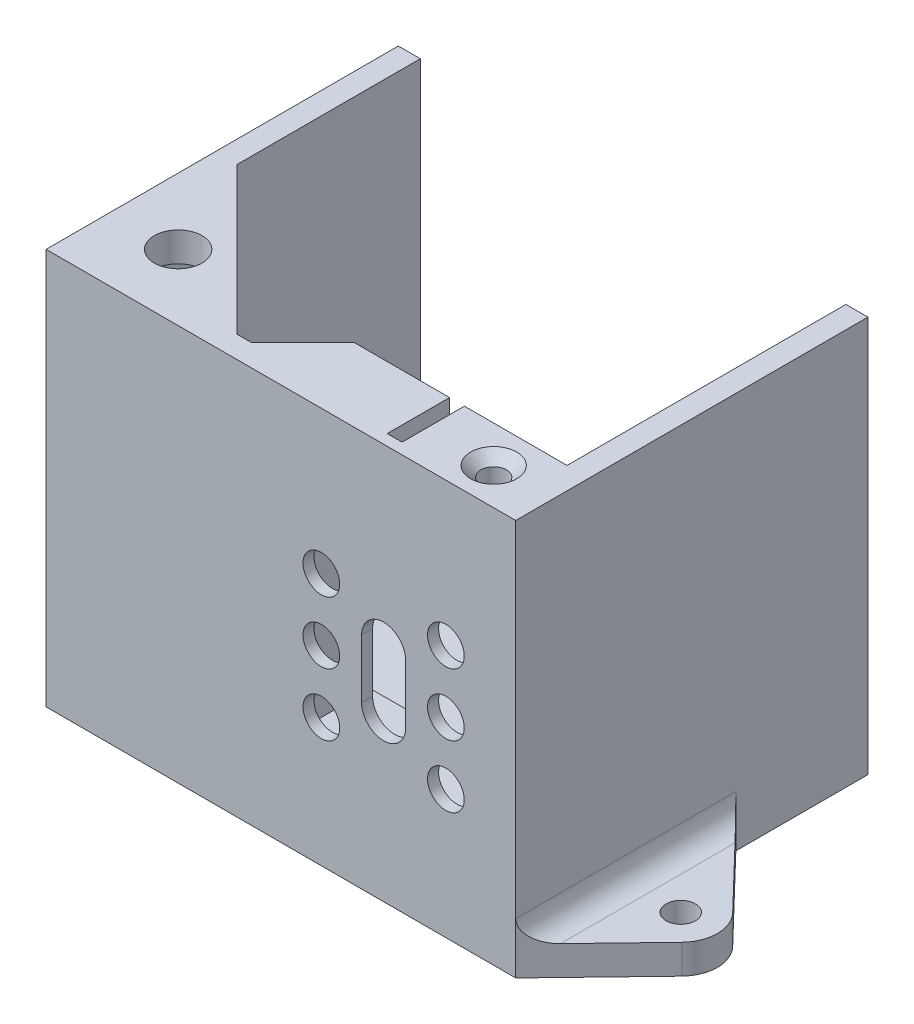
SolidWorks part; units mm, degrees
ref_plane "Płaszczyzna przednia" through (0, 0, 0) normal (0, 0, 1) x (1, 0, 0)
ref_plane "Płaszczyzna górna" through (0, 0, 0) normal (0, 1, 0) x (1, 0, 0)
ref_plane "Płaszczyzna prawa" through (0, 0, 0) normal (1, 0, 0) x (0, 0, -1)
sketch "Sketch1" plane through (0, 0, 0) normal (0, 1, 0) x (1, 0, 0)
  line L1 (-32, 24) -> (32, 24)
  line L2 (-32, 24) -> (-32, -24)
  line L3 (-32, -24) -> (32, -24)
  line L4 (32, 24) -> (32, -24)
  line L5 (-32, 24) -> (32, -24) construction
  line L6 (-32, -24) -> (32, 24) construction
  point P0 (0, 0)
  dimension "D1" = 64
  dimension "D2" = 48
extrude "Boss-Extrude1" add sketch "Sketch1" along normal blind 4
sketch "Sketch2" plane through (0, 0, 0) normal (0, -1, 0) x (1, 0, 0)
  line L9 (-20.6514, -16) -> (-22.3257, -13.1)
  line L10 (-22.3257, -13.1) -> (-25.6743, -13.1)
  line L11 (-25.6743, -13.1) -> (-27.3486, -16)
  line L12 (-27.3486, -16) -> (-25.6743, -18.9)
  line L13 (-25.6743, -18.9) -> (-22.3257, -18.9)
  line L14 (-22.3257, -18.9) -> (-20.6514, -16)
  line L15 (-32, -24) -> (-32, 24) construction
  line L16 (32, -24) -> (-32, -24) construction
  circle A0 centre (-24, -16) radius 2.9 construction
  dimension "D3" = 5.8
  dimension "D1" = 8
  dimension "D2" = 8
extrude "Cut-Extrude1" cut sketch "Sketch2" against normal blind 2.4
sketch "Sketch4" plane through (0, 0, 0) normal (0, -1, 0) x (1, 0, 0)
  line L0 (-32, -24) -> (-32, 24) construction
  line L1 (9.3486, 10) -> (7.6743, 12.9)
  line L2 (7.6743, 12.9) -> (4.3257, 12.9)
  line L3 (4.3257, 12.9) -> (2.6514, 10)
  line L4 (2.6514, 10) -> (4.3257, 7.1)
  line L5 (4.3257, 7.1) -> (7.6743, 7.1)
  line L6 (7.6743, 7.1) -> (9.3486, 10)
  line L8 (32, -24) -> (-32, -24) construction
  circle A0 centre (6, 10) radius 2.9 construction
  dimension "D3" = 5.8
  dimension "D1" = 38
  dimension "D2" = 34
extrude "Cut-Extrude2" cut sketch "Sketch4" against normal blind 2.4
sketch "Sketch6" plane through (0, 4, 0) normal (0, 1, 0) x (1, 0, 0)
  line L0 (-29, 21) -> (-29, 24)
  line L1 (-32, 24) -> (32, 24)
  line L2 (-32, 24) -> (-32, -24)
  line L3 (-32, -24) -> (32, -24)
  line L4 (32, 24) -> (32, -24)
  line L5 (-29, 21) -> (29, 21)
  line L6 (-29, 21) -> (-29, -21)
  line L7 (-29, -21) -> (29, -21)
  line L8 (29, 21) -> (29, -21)
  line L9 (-29, 21) -> (29, -21) construction
  line L10 (-29, -21) -> (29, 21) construction
  line L11 (29, 21) -> (29, 24)
  point P6 (0, 0)
  line M1 (32, -24) -> (32, 24)
  line M2 (32, 24) -> (-32, 24)
  line M3 (-32, 24) -> (-32, -24)
  line M4 (-32, -24) -> (32, -24)
  dimension "D1" = 58
  dimension "D2" = 42
extrude "Boss-Extrude3" add sketch "Sketch6" along normal blind 50 contours L11 L8 L7 L6 L0 M2 M3 M4 M1 region at (-29.8, 4, 0)
sketch "Sketch9" plane through (0, 4, 0) normal (0, 1, 0) x (1, 0, 0)
  line L0 (1, -13) -> (-7, -21)
  line L3 (29, -13) -> (1, -13)
  line L5 (-29, -21) -> (29, -21) construction
  line L6 (-7, -21) -> (29, -21)
  line L7 (1, -13) -> (-7, -21)
  line L9 (29, -21) -> (29, -13)
  line M3 (29, -21) -> (29, 24)
  line M6 (-29, -21) -> (29, -21)
  dimension "D1" = 8
  dimension "D2" = 8
  dimension "D3" = 28
extrude "Boss-Extrude4" add sketch "Sketch9" along normal blind 50 contours L3 L0 M3 M6 region at (12.9167, 4, 17.1667)
sketch "Sketch10" plane through (0, 0, 13) normal (0, 0, -1) x (-1, 0, 0)
  line L0 (-29, 54) -> (-29, 4) construction
  line L1 (-26.75, 38.75) -> (-1.25, 38.75)
  line L2 (-26.75, 38.75) -> (-26.75, 13.25)
  line L3 (-26.75, 13.25) -> (-1.25, 13.25)
  line L4 (-1.25, 38.75) -> (-1.25, 13.25)
  line L5 (-26.75, 38.75) -> (-1.25, 13.25) construction
  line L6 (-26.75, 13.25) -> (-1.25, 38.75) construction
  line L7 (-14, 38.75) -> (-14, 54) construction
  line L9 (-29, 54) -> (-1, 54) construction
  line L15 (-15.0119, 38.75) -> (-12.9881, 38.75)
  line L16 (-15.0119, 38.75) -> (-15.0119, 54)
  line L17 (-15.0119, 54) -> (-12.9881, 54)
  line L18 (-12.9881, 38.75) -> (-12.9881, 54)
  line L19 (-15.0119, 38.75) -> (-12.9881, 54) construction
  line L20 (-15.0119, 54) -> (-12.9881, 38.75) construction
  point P0 (-14, 26)
  point P9 (-14, 46.375)
  line M5 (-1, 54) -> (-29, 54)
  dimension "D1" = 25.5
  dimension "D2" = 25.5
  dimension "D3" = 15
  dimension "D5" = 28
extrude "Cut-Extrude4" cut sketch "Sketch10" against normal blind 9.5 contours L1 L18 L16 M5 | L4 L1 L2 L3 region at (14, 26, 13) region at (14, 46.375, 13)
sketch "Sketch13" plane through (0, 54, 0) normal (0, 1, 0) x (1, 0, 0)
  line L1 (29, -13) -> (-7.9463, -13)
  line L2 (29, -13) -> (29, -14)
  line L3 (29, -14) -> (-7.9463, -14)
  line L4 (-7.9463, -13) -> (-7.9463, -14)
  dimension "D1" = 1
extrude "Cut-Extrude6" cut sketch "Sketch13" against normal blind 32
sketch "Sketch15" plane through (0, 54, 0) normal (0, 1, 0) x (1, 0, 0)
  line L0 (-29, -1) -> (-9, -21)
  line L5 (-29, 24) -> (-29, -21) construction
  line L6 (-29, -21) -> (-7, -21) construction
  line L7 (-29, 24) -> (-29, -21) construction
  line L8 (-29, -1) -> (-29, -21)
  line L9 (-29, -21) -> (-9, -21)
  line L10 (-32, 24) -> (-32, -24) construction
  line L11 (-32, -24) -> (32, -24) construction
  circle A0 centre (-23, -15) radius 3.25
  dimension "D3" = 9
  dimension "D5" = 6.5
  dimension "D1" = 20
  dimension "D2" = 20
  dimension "D4" = 9
extrude "Boss-Extrude5" add sketch "Sketch15" against normal blind 4
sketch "Sketch17" plane through (0, 54, 0) normal (0, 1, 0) x (1, 0, 0)
  line L0 (32, -24) -> (32, 24) construction
  line L7 (-32, -24) -> (32, -24) construction
  line L8 (24, -19) -> (24, -24) construction
  line L9 (24, -19) -> (32, -19) construction
  line L11 (24, -15.6514) -> (21.1, -17.3257)
  line L12 (21.1, -17.3257) -> (21.1, -20.6743)
  line L13 (21.1, -20.6743) -> (24, -22.3486)
  line L14 (24, -22.3486) -> (26.9, -20.6743)
  line L15 (26.9, -20.6743) -> (26.9, -17.3257)
  line L16 (26.9, -17.3257) -> (24, -15.6514)
  circle A0 centre (24, -19) radius 2.9 construction
  dimension "D1" = 8
  dimension "D3" = 5.8
  dimension "D2" = 5
extrude "Cut-Extrude7" cut sketch "Sketch17" against normal blind 7
sketch "Sketch18" plane through (0, 0, 14) normal (0, 0, -1) x (-1, 0, 0)
  line L0 (-15.0119, 54) -> (-29, 54) construction
  line L1 (-26.9, 49.6) -> (-21.1, 49.6)
  line L2 (-26.9, 49.6) -> (-26.9, 47)
  line L3 (-26.9, 47) -> (-21.1, 47)
  line L4 (-21.1, 49.6) -> (-21.1, 47)
  line L5 (-32, 54) -> (-32, 0) construction
  point P6 (-24, 49.6)
  dimension "D1" = 7
  dimension "D2" = 2.6
  dimension "D3" = 5.8
  dimension "D4" = 8
extrude "Cut-Extrude8" cut sketch "Sketch18" against normal blind 5
sketch "Sketch19" plane through (0, 54, 0) normal (0, 1, 0) x (1, 0, 0)
  line L0 (25.75, -19) -> (22.25, -19) construction
  line L6 (22.25, -19) -> (24, -17.25) construction
  line L8 (24, -17.25) -> (24, -20.75) construction
  line L10 (20.7023, -15.4012) -> (27.2977, -15.4012)
  line L11 (20.7023, -15.4012) -> (20.7023, -22.5988)
  line L12 (20.7023, -22.5988) -> (27.2977, -22.5988)
  line L13 (27.2977, -15.4012) -> (27.2977, -22.5988)
  line L14 (20.7023, -22.5988) -> (27.2977, -22.5988)
  line L15 (20.7023, -22.5988) -> (20.7023, -15.4012)
  line L16 (20.7023, -15.4012) -> (27.2977, -15.4012)
  line L17 (27.2977, -22.5988) -> (27.2977, -15.4012)
  line L18 (20.7023, -22.5988) -> (27.2977, -15.4012) construction
  line L19 (20.7023, -15.4012) -> (27.2977, -22.5988) construction
  circle A0 centre (24, -19) radius 1.75
  line M1 (24, -15.6514) -> (26.9, -17.3257)
  line M2 (26.9, -17.3257) -> (26.9, -20.6743)
  line M3 (26.9, -20.6743) -> (24, -22.3486)
  line M4 (24, -22.3486) -> (21.1, -20.6743)
  line M5 (21.1, -20.6743) -> (21.1, -17.3257)
  line M6 (21.1, -17.3257) -> (24, -15.6514)
  dimension "D1" = 3.5
extrude "Boss-Extrude8" add sketch "Sketch19" against normal blind 4.4 contours A0 M1 M6 M5 M4 M3 M2 region at (25.4057, 54, 16.5653)
fillet "Fillet1" radius 1.5 2 edges at (-29, 50, 11) (-19, 50, 21)
sketch "Sketch20" plane through (0, 0, 0) normal (0, -1, 0) x (1, 0, 0)
  line L0 (32, 24) -> (43.1021, 12.4677)
  line L1 (39.5, 9) -> (32, 9) construction
  line L2 (32, -6) -> (43.1021, 5.5323)
  line L3 (-32, -24) -> (-42.9789, -14.5912)
  line L4 (32, -6) -> (32, 24)
  line L6 (-32, 2) -> (-32, -24)
  line L8 (-39.5, -11) -> (-32, -11) construction
  line L9 (-32, 2) -> (-42.9789, -7.4088)
  line L10 (-20.8246, -16) -> (-22.4123, -13.25) construction
  line L11 (-22.4123, -18.75) -> (-20.8246, -16) construction
  line L12 (-25.5877, -18.75) -> (-22.4123, -18.75) construction
  line L13 (-27.1754, -16) -> (-25.5877, -18.75) construction
  line L14 (-25.5877, -13.25) -> (-27.1754, -16) construction
  line L15 (-22.4123, -13.25) -> (-25.5877, -13.25) construction
  line L16 (9.1754, 10) -> (7.5877, 12.75) construction
  line L17 (7.5877, 7.25) -> (9.1754, 10) construction
  line L18 (4.4123, 7.25) -> (7.5877, 7.25) construction
  line L19 (2.8246, 10) -> (4.4123, 7.25) construction
  line L20 (4.4123, 12.75) -> (2.8246, 10) construction
  line L21 (7.5877, 12.75) -> (4.4123, 12.75) construction
  line L22 (-22.3257, -13.1) -> (-25.6743, -13.1) construction
  line L23 (-20.6514, -16) -> (-22.3257, -13.1) construction
  line L24 (-22.3257, -13.1) -> (-25.6743, -13.1) construction
  line L25 (-20.6514, -16) -> (-22.3257, -13.1) construction
  line L26 (32, -24) -> (32, 24)
  line L27 (32, 24) -> (-32, 24)
  line L28 (-32, 24) -> (-32, -24)
  line L29 (-32, -24) -> (32, -24)
  line L30 (32, -6) -> (32, 24)
  line L32 (-32, 2) -> (-32, -24)
  line L36 (9.3486, 10) -> (7.6743, 12.9)
  line L37 (7.6743, 7.1) -> (9.3486, 10)
  line L38 (4.3257, 7.1) -> (7.6743, 7.1)
  line L39 (2.6514, 10) -> (4.3257, 7.1)
  line L40 (4.3257, 12.9) -> (2.6514, 10)
  line L41 (7.6743, 12.9) -> (4.3257, 12.9)
  line L42 (9.3486, 10) -> (7.6743, 12.9) construction
  line L43 (7.6743, 7.1) -> (9.3486, 10) construction
  line L44 (4.3257, 7.1) -> (7.6743, 7.1) construction
  line L45 (2.6514, 10) -> (4.3257, 7.1) construction
  line L46 (4.3257, 12.9) -> (2.6514, 10) construction
  line L47 (7.6743, 12.9) -> (4.3257, 12.9) construction
  line L48 (-20.6514, -16) -> (-22.3257, -13.1)
  line L49 (-22.3257, -18.9) -> (-20.6514, -16)
  line L50 (-25.6743, -18.9) -> (-22.3257, -18.9)
  line L51 (-27.3486, -16) -> (-25.6743, -18.9)
  line L52 (-25.6743, -13.1) -> (-27.3486, -16)
  line L53 (-22.3257, -13.1) -> (-25.6743, -13.1)
  line L54 (-20.6514, -16) -> (-22.3257, -13.1) construction
  line L55 (-22.3257, -18.9) -> (-20.6514, -16) construction
  line L56 (-25.6743, -18.9) -> (-22.3257, -18.9) construction
  line L57 (-27.3486, -16) -> (-25.6743, -18.9) construction
  line L58 (-25.6743, -13.1) -> (-27.3486, -16) construction
  line L59 (-22.3257, -13.1) -> (-25.6743, -13.1) construction
  circle A0 centre (39.5, 9) radius 2
  circle A1 centre (-39.5, -11) radius 2
  arc A2 (43.1021, 5.5323) -> (43.1021, 12.4677) centre (39.5, 9) ccw
  arc A3 (-42.5162, -7.0122) -> (-42.5162, -14.9878) centre (-39.5, -11) ccw
  dimension "D1" = 0
  dimension "D2" = 0
  dimension "D3" = 0
extrude "Boss-Extrude9" add sketch "Sketch20" against normal blind 4 contours L9 A3 L3 L23 A1 | L2 A2 L0 L4 A0 region at (36.4432, 0, 9) region at (-36.5396, 0, -11)
fillet "Fillet2" radius 3 2 edges at (-32, 4, -11) (32, 4, 9)
sketch "Sketch22" plane through (0, 2.4, 0) normal (0, -1, 0) x (1, 0, 0)
  line L0 (4.3257, 12.9) -> (7.6743, 7.1) construction
  line L1 (7.6743, 7.1) -> (7.6743, 12.9) construction
  line L2 (7.6743, 12.9) -> (4.3257, 7.1) construction
  line L3 (-25.6743, -18.9) -> (-22.3257, -13.1) construction
  line L4 (-22.3257, -13.1) -> (-22.3257, -18.9) construction
  line L5 (-25.6743, -13.1) -> (-22.3257, -18.9) construction
  circle A0 centre (-24, -16) radius 1.75
  circle A1 centre (6, 10) radius 1.75
  dimension "D1" = 3.5
  dimension "D2" = 3.5
extrude "Cut-Extrude9" cut sketch "Sketch22" against normal blind 2
sketch "Sketch23" plane through (0, 0, 22.5) normal (0, 0, -1) x (-1, 0, 0)
  line L0 (-14, 13.25) -> (-14, 38.6846) construction
  line L1 (-26.75, 13.25) -> (-1.25, 13.25) construction
  line L2 (-14, 26) -> (-14, 22) construction
  line L3 (-14, 26) -> (-14, 30) construction
  line L4 (-14, 30) -> (-14, 22) construction
  line L5 (-11, 30) -> (-11, 22)
  line L6 (-17, 30) -> (-17, 22)
  line L7 (-14, 38.6846) -> (-14, 54) construction
  line L9 (-12.9881, 54) -> (-15.0119, 54) construction
  line L10 (-22.4853, 17.5147) -> (-5.5147, 17.5147) construction
  line L11 (-22.4853, 34.4853) -> (-22.4853, 17.5147) construction
  line L12 (-5.5147, 34.4853) -> (-5.5147, 17.5147) construction
  line L13 (-14, 26) -> (-1.25, 26) construction
  line L14 (-1.25, 38.75) -> (-1.25, 13.25) construction
  line L15 (-1.25, 26) -> (-26.75, 26) construction
  line L16 (-26.75, 38.75) -> (-26.75, 13.25) construction
  line L17 (-22.4853, 17.5147) -> (-22.4853, 34.4853) construction
  line L18 (-22.4853, 34.4853) -> (-5.5147, 34.4853) construction
  line L19 (-5.5147, 17.5147) -> (-5.5147, 34.4853) construction
  line L20 (-22.4853, 17.5147) -> (-5.5147, 34.4853) construction
  line L21 (-22.4853, 34.4853) -> (-5.5147, 17.5147) construction
  circle A1 centre (-22.4853, 34.4853) radius 2.5
  circle A2 centre (-5.5147, 34.4853) radius 2.5
  circle A3 centre (-5.5147, 17.5147) radius 2.5
  circle A4 centre (-22.4853, 17.5147) radius 2.5
  arc A6 (-11, 30) -> (-17, 30) centre (-14, 30) ccw
  arc A7 (-17, 22) -> (-11, 22) centre (-14, 22) ccw
  circle A8 centre (-22.4853, 26) radius 2.5
  circle A9 centre (-5.5147, 26) radius 2.5
  point P2 (0, 0)
  point P3 (0, 0)
  point P19 (-14, 26)
  point P37 (-14, 26)
  dimension "D5" = 5
  dimension "D6" = 5
  dimension "D7" = 12
  dimension "D8" = 12
  dimension "D2" = 5
  dimension "D3" = 5
  dimension "D1" = 5
  dimension "D4" = 5
extrude "Cut-Extrude10" cut sketch "Sketch23" against normal blind 3
sketch "Sketch26" plane through (0, 54, 0) normal (0, 1, 0) x (1, 0, 0)
  point P0 (24, -19)
hole_wizard "CSK for M3 Countersunk Flat Head Screw1" positions "Sketch26" profile "Sketch25" countersink size "M3" standard "ISO" end condition through all
sketch "Sketch25" plane through (24, 54, 19) normal (1, 0, 0) x (0, 0, 1)
  line L0 (0, 0) -> (0, 54)
  line L1 (0, 54) -> (1.6, 54)
  line L2 (1.6, 54) -> (1.6, 1.55)
  line L3 (1.6, 1.55) -> (3.15, 0)
  line L5 (3.15, 0) -> (0, 0)
  line L6 (-1.6, 1.55) -> (-3.15, 0) construction
  line L11 (0, -6.35) -> (0, 107.95) construction
  dimension "Thru Hole Dia." = 3.2
  dimension "Thru Hole Depth" = 54
  dimension "Near C'Sink Dia." = 6.3
  dimension "Near C'Sink Angle" = 90
